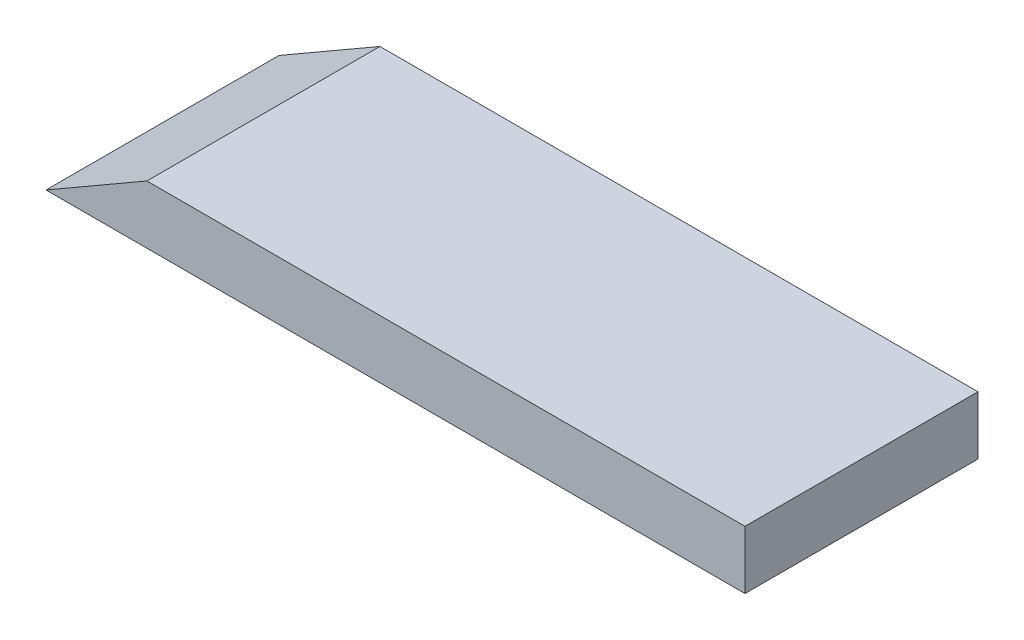
SolidWorks part; units mm, degrees
ref_plane "Front Plane" through (0, 0, 0) normal (0, 0, 1) x (1, 0, 0)
ref_plane "Top Plane" through (0, 0, 0) normal (0, 1, 0) x (1, 0, 0)
ref_plane "Right Plane" through (0, 0, 0) normal (1, 0, 0) x (0, 0, -1)
sketch "Sketch1" plane through (0, 0, 0) normal (0, 1, 0) x (1, 0, 0)
  line L0 (-72.1486, 0) -> (72.1486, 0) construction
  line L1 (0, 32.8959) -> (0, -32.8959) construction
  line L3 (-38.1, -12.7) -> (38.1, -12.7)
  line L4 (-38.1, -12.7) -> (-38.1, 12.7)
  line L5 (-38.1, 12.7) -> (38.1, 12.7)
  line L6 (38.1, -12.7) -> (38.1, 12.7)
  line L7 (0, 12.7) -> (0, -12.7) construction
  line L8 (-38.1, 0) -> (38.1, 0) construction
  point P0 (0, 0)
  point P4 (0, 0)
  point P8 (0, 0)
  dimension "D1" = 25.4
  dimension "D2" = 76.2
extrude "Boss-Extrude1" add sketch "Sketch1" along normal mid plane 6.35 contours L4 L3 L6 L5
chamfer "Chamfer8" distance 6.35 angle 60 1 edges at (-38.1, 3.175, 0) tangent propagation no first distance on face at (-38.1, 0, 0)
